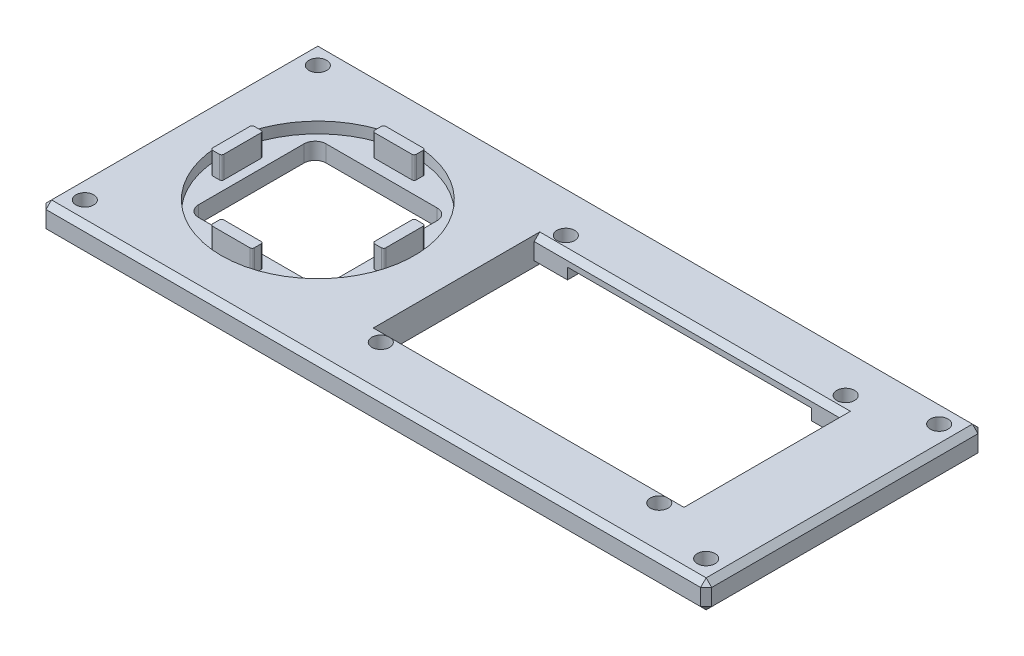
SolidWorks part; units mm, degrees
ref_plane "Front Plane" through (0, 0, 0) normal (0, 0, 1) x (1, 0, 0)
ref_plane "Top Plane" through (0, 0, 0) normal (0, 1, 0) x (1, 0, 0)
ref_plane "Right Plane" through (0, 0, 0) normal (1, 0, 0) x (0, 0, -1)
sketch "Sketch1" plane through (0, 0, 0) normal (0, 1, 0) x (1, 0, 0)
  line L1 (0, 0) -> (120, 0)
  line L2 (0, 0) -> (0, 50)
  line L3 (0, 50) -> (120, 50)
  line L4 (120, 0) -> (120, 50)
  dimension "D1" = 120
  dimension "D2" = 50
extrude "Boss-Extrude1" add sketch "Sketch1" along normal blind 5
sketch "Sketch2" plane through (0, 5, 0) normal (0, 1, 0) x (1, 0, 0)
  line L0 (0, 25) -> (25, 25) construction
  line L1 (0, 50) -> (0, 0) construction
  line L2 (25, 25) -> (10, 25) construction
  line L3 (9.3, 29) -> (9.3, 21)
  line L4 (8.5, 29) -> (11.5, 29)
  line L5 (8.5, 29) -> (8.5, 21)
  line L6 (8.5, 21) -> (11.5, 21)
  line L7 (11.5, 29) -> (11.5, 21)
  line L8 (8.5, 29) -> (11.5, 21) construction
  line L9 (8.5, 21) -> (11.5, 29) construction
  point P13 (25, 25)
  dimension "D1" = 25
  dimension "D2" = 15
  dimension "D3" = 3
  dimension "D4" = 8
  dimension "D5" = 0.8
sketch "Sketch4" plane through (0, 5, 0) normal (0, 1, 0) x (1, 0, 0)
  circle A0 centre (25, 25) radius 17.4
  dimension "D1" = 34.8
extrude "Cut-Extrude3" cut sketch "Sketch4" against normal blind 2
sketch "Sketch3" plane through (0, 5, 0) normal (0, 1, 0) x (1, 0, 0)
  line L1 (15, 36.5) -> (35, 36.5)
  line L2 (13, 34.5) -> (13, 15.5)
  line L3 (15, 13.5) -> (35, 13.5)
  line L4 (37, 34.5) -> (37, 15.5)
  line L5 (13, 36.5) -> (37, 13.5) construction
  line L6 (13, 13.5) -> (37, 36.5) construction
  arc A0 (15, 36.5) -> (13, 34.5) centre (15, 34.5) ccw
  arc A1 (13, 15.5) -> (15, 13.5) centre (15, 15.5) ccw
  arc A2 (35, 13.5) -> (37, 15.5) centre (35, 15.5) ccw
  arc A3 (35, 36.5) -> (37, 34.5) centre (35, 34.5) cw
  point P0 (25, 25)
  dimension "D3" = 2
  dimension "D1" = 23
  dimension "D2" = 24
extrude "Cut-Extrude2" cut sketch "Sketch3" against normal blind 5
sketch "Sketch5" plane through (0, 3, 0) normal (0, 1, 0) x (1, 0, 0)
  line L0 (11.5, 25) -> (9.3, 25) construction
  line L5 (11.5, 29) -> (11.5, 21) construction
  line L6 (9.3, 29) -> (9.3, 21) construction
  line L8 (9.8, 28.75) -> (11, 28.75)
  line L9 (9.4, 28.35) -> (9.4, 21.65)
  line L10 (9.8, 21.25) -> (11, 21.25)
  line L11 (11.4, 28.35) -> (11.4, 21.65)
  line L12 (9.4, 28.75) -> (11.4, 21.25) construction
  line L13 (9.4, 21.25) -> (11.4, 28.75) construction
  arc A0 (11, 21.25) -> (11.4, 21.65) centre (11, 21.65) ccw
  arc A1 (9.4, 21.65) -> (9.8, 21.25) centre (9.8, 21.65) ccw
  arc A2 (11, 28.75) -> (11.4, 28.35) centre (11, 28.35) cw
  arc A3 (9.8, 28.75) -> (9.4, 28.35) centre (9.8, 28.35) ccw
  point P8 (10.4, 25)
  dimension "D3" = 0.4
  dimension "D1" = 2
  dimension "D2" = 7.5
extrude "Boss-Extrude2" add sketch "Sketch5" along normal blind 4
ref_axis "Axis1" through (25, 5, -25) along (0, 1, 0)
pattern_circular "CirPattern1" count 4 over 360 about axis through (25, 5, -25) along (0, 1, 0) of "Boss-Extrude2"
sketch "Sketch6" plane through (0, 5, 0) normal (0, 1, 0) x (1, 0, 0)
  line L0 (0, 50) -> (4, 50) construction
  line L1 (120, 50) -> (0, 50) construction
  line L2 (4, 50) -> (4, 46) construction
  line L3 (120, 0) -> (120, 50) construction
  line L4 (0, 0) -> (120, 0) construction
  line L5 (0, 50) -> (0, 0) construction
  circle A0 centre (4, 46) radius 1.6
  circle A1 centre (116, 46) radius 1.6
  circle A2 centre (116, 4) radius 1.6
  circle A3 centre (4, 4) radius 1.6
  dimension "D2" = 3.2
  dimension "D5" = 4
  dimension "D1" = 4
  dimension "5" = 4
  dimension "D3" = 4
  dimension "D4" = 4
  dimension "D6" = 4
  dimension "D7" = 4
  dimension "D8" = 4
extrude "Cut-Extrude4" cut sketch "Sketch6" against normal through all
sketch "Sketch7" plane through (0, 5, 0) normal (0, 1, 0) x (1, 0, 0)
  line L0 (120, 25) -> (50, 25) construction
  line L1 (120, 0) -> (120, 50) construction
  line L2 (50, 25) -> (50, 5) construction
  line L3 (50, 5) -> (106, 5) construction
  line L4 (78, 45) -> (78, 5) construction
  line L5 (106, 5) -> (50, 5)
  line L6 (106, 5) -> (106, 45)
  line L7 (106, 45) -> (50, 45)
  line L8 (50, 5) -> (50, 45)
  circle A0 centre (103.0994, 42.0451) radius 1.6
  circle A1 centre (103.0998, 8.4451) radius 1.6
  circle A2 centre (52.9, 41.8) radius 1.6
  circle A3 centre (52.9, 8.4451) radius 1.6
  dimension "D7" = 3.2
  dimension "D8" = 3.2
  dimension "D9" = 3.2
  dimension "D10" = 3.2
  dimension "D1" = 70
  dimension "D2" = 20
  dimension "D3" = 56
  dimension "D4" = 40
  dimension "D5" = 33.6
  dimension "D6" = 50.2
  dimension "D11" = 16.8
  dimension "D12" = 25.1
sketch "Sketch8" plane through (0, 5, 0) normal (0, 1, 0) x (1, 0, 0)
  line L0 (50, 5) -> (50, 45) construction
  line L1 (50, 39) -> (106, 39)
  line L2 (50, 39) -> (50, 11)
  line L3 (50, 11) -> (106, 11)
  line L4 (106, 39) -> (106, 11)
  line L5 (106, 5) -> (106, 45) construction
  line L6 (106, 45) -> (50, 45) construction
  line L7 (106, 5) -> (50, 5) construction
  dimension "D1" = 6
  dimension "D2" = 6
extrude "Cut-Extrude5" cut sketch "Sketch8" against normal through all
sketch "Sketch9" plane through (0, 0, 0) normal (0, 1, 0) x (1, 0, 0)
  line L0 (106, 45) -> (50, 45) construction
  line L1 (56, 45) -> (100, 45)
  line L2 (56, 45) -> (56, 5)
  line L3 (56, 5) -> (100, 5)
  line L4 (100, 45) -> (100, 5)
  line L5 (106, 5) -> (50, 5) construction
  line L6 (50, 5) -> (50, 45) construction
  line L7 (106, 5) -> (106, 45) construction
  dimension "D1" = 6
  dimension "D2" = 6
extrude "Cut-Extrude6" cut sketch "Sketch9" along normal blind 3
sketch "Sketch10" plane through (0, 0, 0) normal (0, -1, 0) x (1, 0, 0)
  line L1 (50, -5) -> (106, -5)
  line L2 (50, -5) -> (50, -45)
  line L3 (50, -45) -> (106, -45)
  line L4 (106, -5) -> (106, -45)
extrude "Cut-Extrude7" cut sketch "Sketch10" against normal blind 1
sketch "Sketch11" plane through (0, 5, 0) normal (0, 1, 0) x (1, 0, 0)
  circle A0 centre (52.9, 41.8) radius 1.6
  circle A1 centre (103.0994, 42.0451) radius 1.6
  circle A2 centre (103.0998, 8.4451) radius 1.6
  circle A3 centre (52.9, 8.4451) radius 1.6
extrude "Cut-Extrude8" cut sketch "Sketch11" against normal through all
chamfer "Chamfer1" distance 1 angle 45 12 edges at (0, 2.5, -50) (60, 5, -50) (120, 2.5, -50) (120, 5, -25) (120, 2.5, 0) (0, 2.5, 0) (0, 5, -25) (60, 5, 0) (120, 0, -25) (60, 0, -50) (0, 0, -25) (60, 0, 0)
chamfer "Chamfer2" distance 1 angle 45 2 edges at (78, 5, -11) (78, 5, -39)
